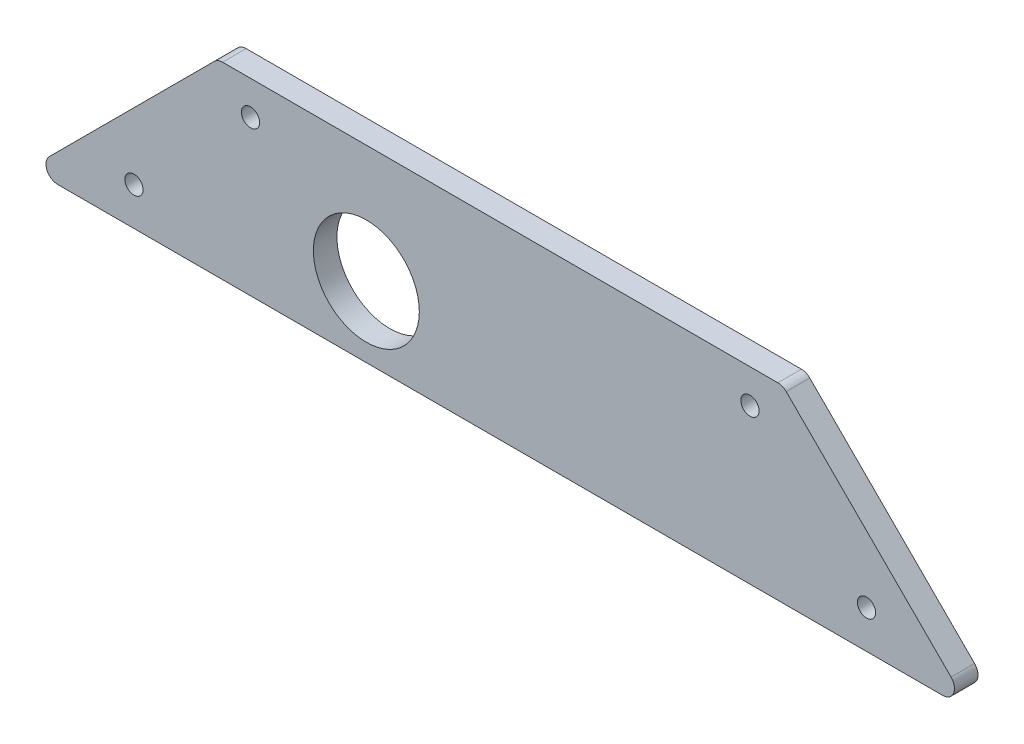
SolidWorks part; units mm, degrees
ref_plane "Front Plane" through (0, 0, 0) normal (0, 0, 1) x (1, 0, 0)
ref_plane "Top Plane" through (0, 0, 0) normal (0, 1, 0) x (1, 0, 0)
ref_plane "Right Plane" through (0, 0, 0) normal (1, 0, 0) x (0, 0, -1)
sketch "Sketch1" plane through (0, 0, 0) normal (0, 0, 1) x (1, 0, 0)
  line L0 (-76.2, 29.1622) -> (-127, -21.6378)
  line L1 (-76.2, 29.1622) -> (76.2, 29.1622)
  line L2 (-127, -21.6378) -> (127, -21.6378)
  line L3 (127, -21.6378) -> (76.2, 29.1622)
  point P0 (0, 0)
  point P1 (0, -21.6378)
  dimension "D1" = 135
  dimension "D2" = 254
  dimension "D3" = 50.8
  dimension "D4" = 135
extrude "Boss-Extrude1" add sketch "Sketch1" along normal mid plane 6.35
sketch "Sketch8" plane through (0, 0, 3.175) normal (0, 0, 1) x (1, 0, 0)
  line L0 (0, 105.3622) -> (-327.0287, -221.6666) construction
  line L1 (0, 69.4411) -> (279.7642, -210.3231) construction
  line L2 (76.2, 29.1622) -> (297.7247, -192.3626) construction
  line L3 (0, 69.4411) -> (-309.0682, -239.6271) construction
  line L4 (76.2, 29.1622) -> (0, 105.3622) construction
  line L5 (14.5597, 84.0009) -> (-309.0682, -239.6271) construction
  line L6 (58.2395, 11.2016) -> (279.7642, -210.3231) construction
  line L7 (-3.4008, 101.9614) -> (-327.0287, -221.6666) construction
  line L8 (98.7828, -11.3812) -> (67.3519, 20.0497) construction
  line L9 (-76.2, 29.1622) -> (-127, -21.6378) construction
  point P2 (67.3519, 20.0497)
  point P6 (98.7828, -11.3812)
  point P16 (-67.3519, 20.0497)
  point P18 (-98.7828, -11.3812)
  dimension "D1" = 25.4
  dimension "D2" = 25.4
  dimension "D3" = 12.7
  dimension "D4" = 107.95
  dimension "D5" = 44.45
  dimension "D6" = 12.7
  dimension "D7" = 12.7
  dimension "D8" = 107.95
  dimension "D9" = 12.7
  dimension "D10" = 44.45
sketch "Sketch2" plane through (0, 0, 3.175) normal (0, 0, 1) x (1, 0, 0)
  line L0 (-127, -21.6378) -> (127, -21.6378) construction
  line L3 (-76.2, 29.1622) -> (-127, -21.6378) construction
  circle A0 centre (-36.108, -2.5878) radius 14.2875
  dimension "D1" = 19.05
  dimension "D2" = 28.575
  dimension "D3" = 50.8
extrude "Cut-Extrude1" cut sketch "Sketch2" against normal through all
hole_wizard "#10 (0.1935) Diameter Hole2" positions "3DSketch1" profile "Sketch9" hole size "#10" standard "ANSI Inch" end condition through all
sketch3d "3DSketch1"
  line L0 (-127, -21.6378, 3.175) -> (-76.2, 29.1622, 3.175) construction
  line L2 (-76.2, 29.1622, 3.175) -> (0, 105.3622, 3.175) construction
  line L3 (0, 105.3622, 3.175) -> (145.7507, -40.3886, 3.175) construction
  line L4 (76.2, 29.1622, 3.175) -> (297.7247, -192.3626, 3.175) construction
  line L5 (145.7507, -40.3886, 3.175) -> (127.7902, -58.3491, 3.175) construction
  line L6 (0, 69.4411, 3.175) -> (279.7642, -210.3231, 3.175) construction
  line L7 (127.7902, -58.3491, 3.175) -> (0, 69.4411, 3.175) construction
  line L8 (0, 69.4411, 3.175) -> (-116.7666, -47.3254, 3.175) construction
  line L9 (0, 69.4411, 3.175) -> (-309.0682, -239.6271, 3.175) construction
  line L10 (-116.7666, -47.3254, 3.175) -> (-134.7271, -29.3649, 3.175) construction
  line L11 (0, 105.3622, 3.175) -> (-327.0287, -221.6666, 3.175) construction
  line L12 (-134.7271, -29.3649, 3.175) -> (-127, -21.6378, 3.175) construction
  point P0 (67.3519, 20.0497, 3.175)
  point P4 (98.7828, -11.3812, 3.175)
  point P8 (-67.3519, 20.0497, 3.175)
  point P34 (-98.7828, -11.3812, 3.175)
  dimension "D1" = 12.7
  dimension "D2" = 107.95
  dimension "D3" = 12.7
  dimension "D6" = 12.7
  dimension "D4" = 107.95
  dimension "D5" = 44.45
sketch "Sketch9" plane through (67.3519, 20.0497, 3.175) normal (1, 0, 0) x (0, -1, 0)
  line L0 (0, 0) -> (0, 6.35)
  line L1 (0, 6.35) -> (2.4574, 6.35)
  line L2 (2.4574, 6.35) -> (2.4574, 0)
  line L5 (2.4574, 0) -> (0, 0)
  line L11 (0, -6.35) -> (0, 107.95) construction
  dimension "Thru Hole Dia." = 4.9149
  dimension "Thru Hole Depth" = 6.35
sketch "Sketch10" plane through (0, 0, 3.175) normal (0, 0, 1) x (1, 0, 0)
  line L0 (17.7736, 51.2937) -> (-36.108, -2.5878) construction
  line L1 (-127, -21.6378) -> (127, -21.6378) construction
  line L2 (-36.108, -2.5878) -> (35.921, 69.4411) construction
  line L3 (76.2, 29.1622) -> (0, 105.3622) construction
  line L4 (-18.1474, -20.5484) -> (53.8815, 51.4806) construction
  line L5 (-54.0685, 15.3727) -> (17.9605, 87.4016) construction
  line L6 (75.9032, 32.2612) -> (-89.7636, -62.5675) construction
  line L7 (68.4053, 57.2362) -> (-102.3818, -40.5234) construction
  line L8 (63.285, 54.3053) -> (-102.3818, -40.5234) construction
  line L9 (34.6116, 68.1317) -> (0.9356, 34.4557) construction
  line L10 (50.6906, 47.0962) -> (9.358, 23.4371) construction
  line L12 (4.2425, 20.509) -> (44.7819, 9.4849) construction
  line L13 (44.7819, 9.4849) -> (55.8061, 50.0243) construction
  line L14 (55.8061, 50.0243) -> (15.2667, 61.0484) construction
  line L15 (15.2667, 61.0484) -> (4.2425, 20.509) construction
  line L16 (-2.0892, 31.4309) -> (37.6364, 31.4309) construction
  line L17 (37.6364, 31.4309) -> (37.6364, 71.1565) construction
  line L18 (37.6364, 71.1565) -> (-2.0892, 71.1565) construction
  line L19 (-2.0892, 71.1565) -> (-2.0892, 31.4309) construction
  circle A0 centre (17.7736, 51.2937) radius 14.2875 construction
  circle A1 centre (67.3519, 20.0497) radius 6.35 construction
  circle A2 centre (-36.108, -2.5878) radius 14.2875 construction
  circle A3 centre (30.0243, 35.2667) radius 14.2875 construction
  circle A4 centre (50.6906, 47.0962) radius 2.5527
  circle A5 centre (9.358, 23.4371) radius 2.5527
  circle A6 centre (0.9356, 34.4557) radius 2.5527
  circle A7 centre (34.6116, 68.1317) radius 2.5527
  circle A8 centre (30.0243, 35.2667) radius 21.0058 construction
  circle A9 centre (17.7736, 51.2937) radius 19.8628 construction
  point P33 (17.7736, 51.2937)
  point P34 (30.0243, 35.2667)
  dimension "D1" = 76.2
  dimension "D5" = 12.7
  dimension "D7" = 76.2
  dimension "D8" = 47.625
  dimension "D9" = 5.1054
  dimension "D2" = 135
  dimension "D3" = 25.4
  dimension "D6" = 25.4
  dimension "D10" = 47.625
  dimension "D11" = 42.0116
  dimension "D12" = 39.7256
  dimension "D4" = 25.4
fillet "Fillet1" radius 3.175 4 edges at (-127, -21.6378, 0) (-76.2, 29.1622, 0) (127, -21.6378, 0) (76.2, 29.1622, 0)
